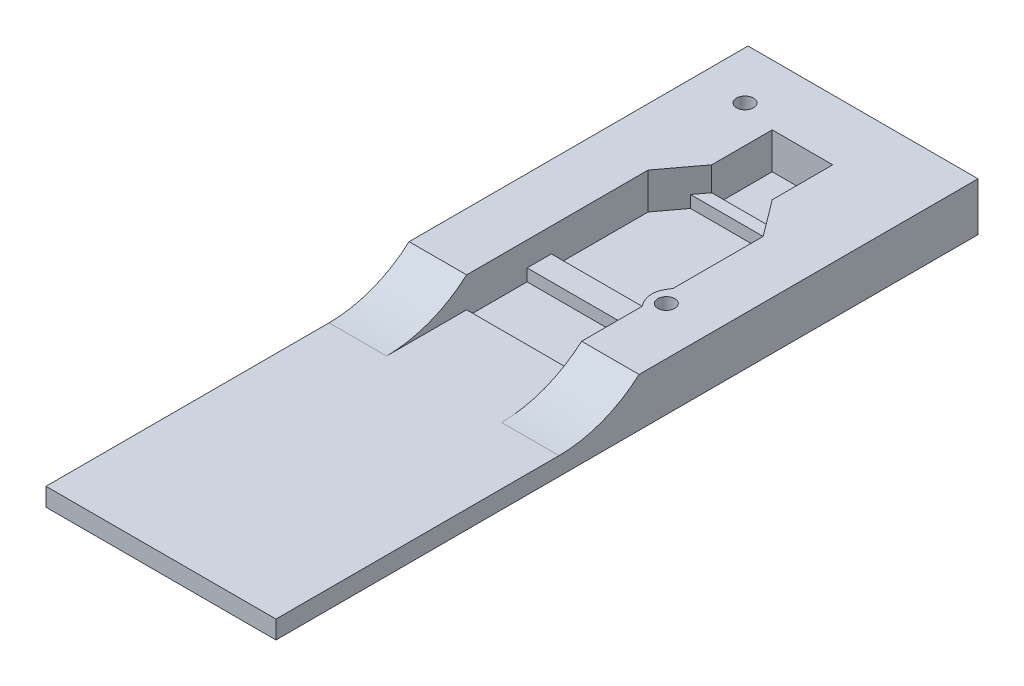
SolidWorks part; units mm, degrees
ref_plane "Front Plane" through (0, 0, 0) normal (0, 0, 1) x (1, 0, 0)
ref_plane "Top Plane" through (0, 0, 0) normal (0, 1, 0) x (1, 0, 0)
ref_plane "Right Plane" through (0, 0, 0) normal (1, 0, 0) x (0, 0, -1)
sketch "Sketch1" plane through (0, 0, 0) normal (0, 1, 0) x (1, 0, 0)
  line L1 (0, 0) -> (13.5, 0)
  line L2 (0, 0) -> (0, 20)
  line L3 (0, 20) -> (13.5, 20)
  line L4 (13.5, 0) -> (13.5, 20)
  dimension "D1" = 20
  dimension "D2" = 13.5
extrude "Boss-Extrude1" add sketch "Sketch1" along normal blind 1
sketch "Sketch2" plane through (0, 1, 0) normal (0, 1, 0) x (1, 0, 0)
  line L0 (2, 10) -> (2, 2)
  line L1 (0, 20) -> (13.5, 20)
  line L2 (0, 20) -> (0, 0)
  line L3 (0, 0) -> (2, 0)
  line L4 (13.5, 20) -> (13.5, 0)
  line L5 (4.25, 13) -> (2, 10)
  line L6 (4.25, 18) -> (4.25, 13)
  line L7 (2, 2) -> (2, 0)
  line L8 (9.25, 18) -> (9.25, 13)
  line L10 (11.5, 10) -> (11.5, 2.5356)
  line L11 (4.25, 18) -> (9.25, 18)
  line L12 (2, 18) -> (11.5, 18) construction
  line L13 (9.25, 13) -> (11.5, 10)
  line L14 (2, 18) -> (2, 2) construction
  line L15 (2, 2) -> (11.5, 2) construction
  line L16 (11.5, 18) -> (11.5, 2) construction
  line L17 (11.5, 0) -> (13.5, 0)
  line L19 (0, 0) -> (13.5, 0) construction
  spline S0 degree 2 poles (11.5, 2.5356) (10.5366, 1.3002) (11.5, 0) knots 0 0 0 1 1 1
  dimension "D1" = 5
  dimension "D2" = 5
  dimension "D4" = 4.25
  dimension "D5" = 4.25
  dimension "D6" = 2
extrude "Boss-Extrude2" add sketch "Sketch2" along normal blind 3
sketch "Sketch3" plane through (0, 1, 0) normal (0, 1, 0) x (1, 0, 0)
  line L0 (4.25, 13) -> (9.25, 13)
  line L1 (9.25, 13) -> (10, 12)
  line L2 (9.25, 13) -> (11.5, 10) construction
  line L3 (10, 12) -> (3.5, 12)
  line L4 (2, 10) -> (4.25, 13) construction
  line L5 (3.5, 12) -> (4.25, 13)
  line L6 (13.5, 20) -> (0, 20) construction
  line L7 (13.5, 0) -> (13.5, 20) construction
  line L8 (0, 20) -> (0, 0) construction
  dimension "D1" = 1
  dimension "D2" = 7
  dimension "D3" = 4.25
  dimension "D4" = 3.5
extrude "Boss-Extrude3" add sketch "Sketch3" along normal blind 1
sketch "Sketch4" plane through (0, 0, 0) normal (0, -1, 0) x (1, 0, 0)
  line L0 (0, -20) -> (0, 0) construction
  line L1 (13.5, -20) -> (0, -20) construction
  line L2 (0, 0) -> (13.5, 0) construction
  line L3 (13.5, 0) -> (13.5, -20) construction
  circle A0 centre (1.2, -18.8) radius 0.7
  circle A1 centre (12.3, -1.2) radius 0.7
  dimension "D1" = 1.2
  dimension "D2" = 1.2
  dimension "D3" = 1.2
  dimension "D4" = 1.2
extrude "Cut-Extrude1" cut sketch "Sketch4" against normal blind 11.5 from offset 1 offset against normal yes
sketch "Sketch5" plane through (0, 1, 0) normal (0, 1, 0) x (1, 0, 0)
  line L0 (11.5, 10) -> (11.5, 2.5356) construction
  line L1 (2, 0) -> (11.5, 0)
  line L2 (2, 0) -> (2, 2)
  line L3 (2, 2) -> (11.5, 2)
  line L4 (11.5, 0) -> (11.5, 2)
  dimension "D1" = 2
extrude "Boss-Extrude4" add sketch "Sketch5" along normal blind 1
sketch "Sketch6" plane through (0, 1, 0) normal (0, 1, 0) x (1, 0, 0)
  line L1 (0, 20) -> (13.5, 20)
  line L2 (0, 20) -> (0, 0)
  line L3 (0, 0) -> (13.5, 0)
  line L4 (13.5, 20) -> (13.5, 0)
  line L5 (-2.75, 23) -> (16.25, 23)
  line L6 (-2.75, 23) -> (-2.75, -5)
  line L7 (-2.75, -5) -> (16.25, -5)
  line L8 (16.25, 23) -> (16.25, -5)
  dimension "D1" = 2.75
  dimension "D2" = 2.75
  dimension "D3" = 3
  dimension "D4" = 5
  dimension "D5" = 19
extrude "Boss-Extrude5" add sketch "Sketch6" against normal blind 1
sketch "Sketch7" plane through (0, 4, 0) normal (0, 1, 0) x (1, 0, 0)
  line L0 (2, 0) -> (2, -5)
  line L1 (0, 20) -> (13.5, 20)
  line L2 (0, 20) -> (0, 0)
  line L3 (0, 0) -> (2, 0)
  line L4 (13.5, 20) -> (13.5, 0)
  line L5 (-2.75, 23) -> (16.25, 23)
  line L6 (-2.75, 23) -> (-2.75, -5)
  line L7 (-2.75, -5) -> (2, -5)
  line L8 (16.25, 23) -> (16.25, -5)
  line L9 (11.5, 0) -> (11.5, -5)
  line L10 (11.5, 0) -> (13.5, 0)
  line L11 (11.5, -5) -> (16.25, -5)
extrude "Boss-Extrude6" add sketch "Sketch7" against normal up to surface (3 mm away) up to face at (6.75, 1, -10)
sketch "Sketch8" plane through (0, 0, 5) normal (0, 0, 1) x (1, 0, 0)
  line L0 (16.25, 0) -> (16.25, 4) construction
  line L1 (-2.75, 0) -> (16.25, 0)
  line L2 (-2.75, 0) -> (-2.75, 1.5)
  line L3 (-2.75, 1.5) -> (16.25, 1.5)
  line L4 (16.25, 0) -> (16.25, 1.5)
  dimension "D1" = 1.5
extrude "Boss-Extrude7" add sketch "Sketch8" along normal blind 30
fillet "Fillet1" radius 10 2 edges
